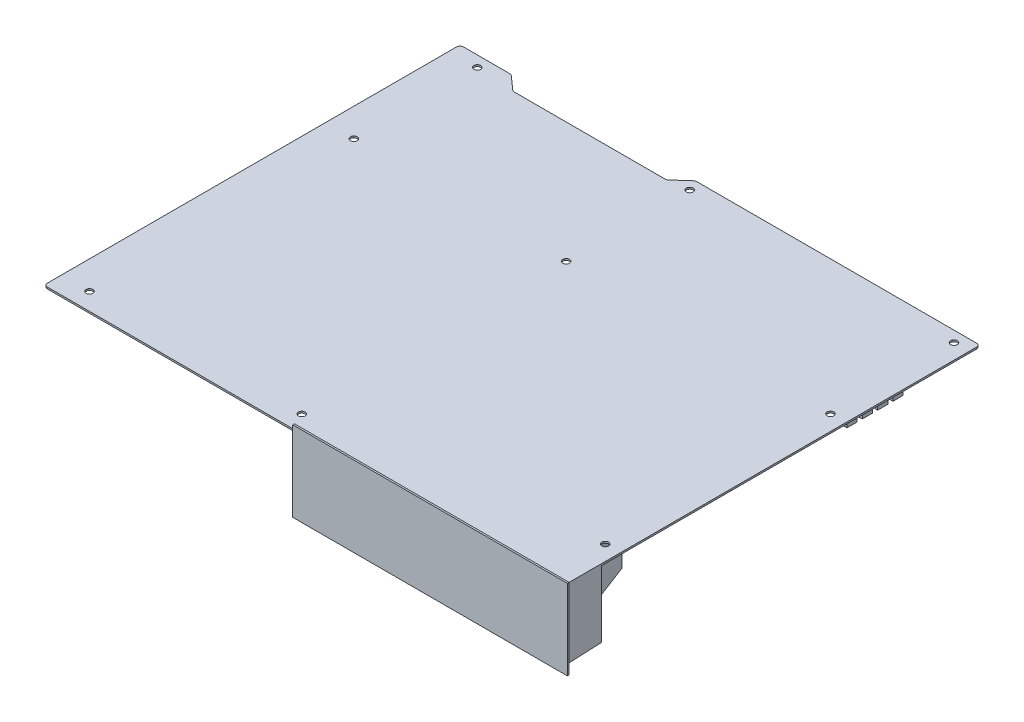
SolidWorks part; units mm, degrees
ref_plane "Front" through (0, 0, 0) normal (0, 0, 1) x (1, 0, 0)
ref_plane "Top" through (0, 0, 0) normal (0, 1, 0) x (1, 0, 0)
ref_plane "Right" through (0, 0, 0) normal (1, 0, 0) x (0, 0, -1)
sketch "Sketch1" plane through (0, 0, 0) normal (0, 1, 0) x (1, 0, 0)
  line L0 (-122.4, 121.92) -> (-122.4, 113.92) construction
  line L2 (-152.4, 121.92) -> (-152.4, -121.92)
  line L3 (-152.4, -121.92) -> (152.4, -121.92)
  line L4 (152.4, 121.92) -> (152.4, -121.92)
  line L7 (-122.4, 113.92) -> (-14.4, 113.92) construction
  line L8 (-14.4, 113.92) -> (-14.4, 121.92) construction
  line L9 (-152.4, 121.92) -> (-122.4, 121.92)
  line L10 (-14.4, 121.92) -> (152.4, 121.92)
  line L11 (-113.4, 113.92) -> (-23.4, 113.92)
  line L12 (-113.4, 113.92) -> (-122.4, 121.92)
  line L13 (-23.4, 113.92) -> (-14.4, 121.92)
  line L14 (-152.4, -111.76) -> (152.4, -111.76) construction
  line L15 (-152.4, 43.18) -> (152.4, 43.18) construction
  line L16 (-152.4, 115.57) -> (152.4, 115.57) construction
  line L17 (-135.89, -121.92) -> (-135.89, 121.92) construction
  line L18 (-11.43, -121.92) -> (-11.43, 115.57) construction
  line L19 (143.51, -121.92) -> (143.51, 121.92) construction
  circle A0 centre (-11.43, -111.76) radius 1.9812
  circle A1 centre (143.51, -88.9) radius 1.9812
  circle A2 centre (-135.89, 43.18) radius 1.9812
  circle A3 centre (-11.43, 115.57) radius 1.9812
  circle A4 centre (-135.89, 115.57) radius 1.9812
  circle A5 centre (143.51, 115.57) radius 1.9812
  circle A6 centre (-135.89, -111.76) radius 1.9812
  circle A7 centre (143.51, 43.18) radius 1.9812
  circle A8 centre (-11.43, 43.18) radius 1.9812
  point P0 (0, 0)
  point P12 (-68.4, 113.92)
  point P13 (-68.4, 113.92)
  dimension "D13" = 3.9624
  dimension "D1" = 304.8
  dimension "D2" = 243.84
  dimension "D3" = 30
  dimension "D4" = 108
  dimension "D5" = 90
  dimension "D6" = 8
  dimension "D7" = 227.33
  dimension "D8" = 10.16
  dimension "D9" = 154.94
  dimension "D10" = 124.46
  dimension "D11" = 279.4
  dimension "D12" = 16.51
  dimension "D14" = 22.86
extrude "Boss-Extrude1" add sketch "Sketch1" along normal blind 1
fillet "Fillet1" radius 2 4 edges at (-14.4, 0.5, -121.92) (-23.4, 0.5, -113.92) (-122.4, 0.5, -121.92) (-113.4, 0.5, -113.92)
fillet "Fillet2" radius 2 3 edges at (-152.4, 0.5, 121.92) (152.4, 0.5, -121.92) (-152.4, 0.5, -121.92)
sketch "Sketch2" plane through (0, 0, 0) normal (0, -1, 0) x (1, 0, 0)
  line L0 (152.4, 121.92) -> (152.4, -119.92) construction
  line L1 (-2.6, 121.92) -> (152.4, 121.92)
  line L2 (-2.6, 121.92) -> (-2.6, 99.92)
  line L4 (152.4, 121.92) -> (152.4, 99.92)
  line L5 (152.4, 99.92) -> (134.32, 91.3694)
  line L6 (134.32, 91.3694) -> (122.5293, 57.92)
  line L7 (-150.4, 121.92) -> (152.4, 121.92) construction
  line L8 (24.5293, 57.92) -> (122.5293, 57.92)
  line L9 (-2.6, 99.92) -> (24.5293, 57.92)
  dimension "D1" = 155
  dimension "D2" = 22
  dimension "D3" = 98
  dimension "D4" = 50
  dimension "D5" = 20
  dimension "D6" = 64
extrude "Boss-Extrude2" add sketch "Sketch2" along normal blind 40
sketch "Sketch3" plane through (0, 0, 121.92) normal (0, 0, 1) x (1, 0, 0)
  line L0 (152.4, -40) -> (-2.6, -40) construction
  line L1 (155.4, -43) -> (-5.6, -43)
  line L2 (155.4, -43) -> (155.4, 4)
  line L3 (155.4, 4) -> (-5.6, 4)
  line L4 (-5.6, -43) -> (-5.6, 4)
  line L5 (-150.4, 1) -> (152.4, 1) construction
  line L6 (152.4, 1) -> (152.4, -40) construction
  line L7 (-2.6, -40) -> (-2.6, 0) construction
  dimension "D1" = 3
  dimension "D2" = 3
  dimension "D3" = 3
  dimension "D4" = 3
extrude "Boss-Extrude3" add sketch "Sketch3" along normal blind 1
sketch "Sketch4" plane through (0, 0, 0) normal (1, 0, 0) x (0, 0, -1)
  line L2 (-55.6754, -37) -> (-121.92, -40)
  line L5 (-55.6754, -37) -> (-55.6754, -43.769)
  line L6 (-55.6754, -43.769) -> (-121.92, -43.769)
  line L7 (-121.92, -43.769) -> (-121.92, -40)
extrude "Cut-Extrude1" cut sketch "Sketch4" along normal mid plane 450
sketch "Sketch5" plane through (0, 0, 0) normal (0, -1, 0) x (1, 0, 0)
  line L0 (150.4, -121.92) -> (-13.6396, -121.92) construction
  line L1 (-2.6, -85.92) -> (137.4, -85.92)
  line L2 (-2.6, -85.92) -> (-2.6, -91.92)
  line L3 (-2.6, -91.92) -> (137.4, -91.92)
  line L4 (137.4, -85.92) -> (137.4, -91.92)
  line L5 (152.4, 99.92) -> (152.4, -119.92) construction
  dimension "D1" = 140
  dimension "D2" = 30
  dimension "D3" = 15
  dimension "D4" = 6
extrude "Boss-Extrude4" add sketch "Sketch5" along normal blind 5
sketch "Sketch6" plane through (0, -5, 0) normal (0, -1, 0) x (1, 0, 0)
  line L0 (-2.6, -91.92) -> (137.4, -91.92) construction
  line L1 (137.4, -85.92) -> (131.4, -85.92)
  line L2 (137.4, -85.92) -> (137.4, -91.92)
  line L3 (137.4, -91.92) -> (131.4, -91.92)
  line L4 (131.4, -85.92) -> (131.4, -91.92)
  line L6 (-2.6, -85.92) -> (3.4, -85.92)
  line L7 (-2.6, -85.92) -> (-2.6, -91.92)
  line L8 (-2.6, -91.92) -> (3.4, -91.92)
  line L9 (3.4, -85.92) -> (3.4, -91.92)
  dimension "D1" = 6
  dimension "D2" = 6
extrude "Boss-Extrude5" add sketch "Sketch6" along normal blind 12
sketch "Sketch7" plane through (0, -17, 0) normal (0, -1, 0) x (1, 0, 0)
  line L1 (-0.1, -88.17) -> (134.9, -88.17)
  line L2 (-0.1, -88.17) -> (-0.1, -89.67)
  line L3 (-0.1, -89.67) -> (134.9, -89.67)
  line L4 (134.9, -88.17) -> (134.9, -89.67)
  line L6 (137.4, -85.92) -> (-2.6, -85.92) construction
  line L8 (137.4, -91.92) -> (137.4, -85.92) construction
  dimension "D1" = 1.5
  dimension "D2" = 2.25
  dimension "D3" = 135
  dimension "D4" = 2.5
extrude "Cut-Extrude2" cut sketch "Sketch7" against normal blind 15
pattern_linear "LPattern2" count 4 spacing 9 along (0, 0, 1) of "Boss-Extrude5", "Cut-Extrude2", "Boss-Extrude4"
sketch "Sketch8" plane through (0, 0, 0) normal (0, -1, 0) x (1, 0, 0)
  line L0 (-152.4, -119.92) -> (-152.4, 119.92) construction
  line L1 (-35.4, 78.92) -> (-29.4, 78.92)
  line L2 (-35.4, 78.92) -> (-35.4, -10.08)
  line L3 (-35.4, -10.08) -> (-29.4, -10.08)
  line L4 (-29.4, 78.92) -> (-29.4, -10.08)
  line L5 (-150.4, 121.92) -> (-5.6, 121.92) construction
  line L6 (-33.4, 76.92) -> (-31.4, 76.92)
  line L7 (-33.4, 76.92) -> (-33.4, -8.08)
  line L8 (-33.4, -8.08) -> (-31.4, -8.08)
  line L9 (-31.4, 76.92) -> (-31.4, -8.08)
  dimension "D1" = 117
  dimension "D2" = 6
  dimension "D3" = 89
  dimension "D4" = 2
  dimension "D5" = 2
  dimension "D6" = 85
  dimension "D7" = 2
  dimension "D8" = 43
extrude "Boss-Extrude6" add sketch "Sketch8" along normal blind 12
sketch "Sketch9" plane through (0, 0, 0) normal (0, -1, 0) x (1, 0, 0)
  line L0 (150.4, -121.92) -> (-13.6396, -121.92) construction
  line L1 (37.4, 13.08) -> (72.4, 13.08)
  line L2 (37.4, 13.08) -> (37.4, -16.92)
  line L3 (37.4, -16.92) -> (72.4, -16.92)
  line L4 (72.4, 13.08) -> (72.4, -16.92)
  line L5 (152.4, 99.92) -> (152.4, -119.92) construction
  dimension "D1" = 105
  dimension "D2" = 30
  dimension "D3" = 35
  dimension "D4" = 80
extrude "Boss-Extrude7" add sketch "Sketch9" along normal blind 10
